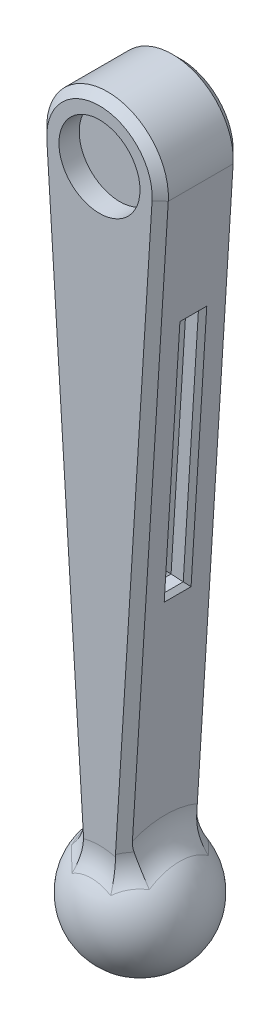
SolidWorks part; units mm, degrees
ref_plane "Front Plane" through (0, 0, 0) normal (0, 0, 1) x (1, 0, 0)
ref_plane "Top Plane" through (0, 0, 0) normal (0, 1, 0) x (1, 0, 0)
ref_plane "Right Plane" through (0, 0, 0) normal (1, 0, 0) x (0, 0, -1)
sketch "Sketch1" plane through (0, 0, 0) normal (0, 0, 1) x (1, 0, 0)
  line L0 (0, 0) -> (0, -160) construction
  line L1 (-14.9707, -0.9375) -> (-4.9902, -160.3125)
  line L2 (14.9707, -0.9375) -> (4.9902, -160.3125)
  arc A0 (14.9707, -0.9375) -> (-14.9707, -0.9375) centre (0, 0) ccw
  arc A1 (-4.9902, -160.3125) -> (4.9902, -160.3125) centre (0, -160) ccw
  dimension "D1" = 30
  dimension "D3" = 10
  dimension "D2" = 160
extrude "Boss-Extrude1" add sketch "Sketch1" along normal mid plane 20
sketch "Sketch2" plane through (0, 0, 10) normal (0, 0, 1) x (1, 0, 0)
  circle A0 centre (0, 0) radius 10
  arc A1 (14.9707, -0.9375) -> (-14.9707, -0.9375) centre (0, 0) ccw construction
  dimension "D1" = 5
extrude "Cut-Extrude1" cut sketch "Sketch2" against normal blind 5
mirror "Mirror1" about plane through (0, 0, 0) normal (0, 0, 1) of "Cut-Extrude1"
sketch "Sketch4" plane through (0, 0, 0) normal (0, 0, 1) x (1, 0, 0)
  line L0 (0, -145) -> (0, -175) construction
  line L1 (0, -145) -> (0, -175)
  arc A0 (0, -145) -> (0, -175) centre (0, -160) ccw
  dimension "D1" = 30
revolve "Revolve1" add sketch "Sketch4" angle 360 about L0
chamfer "Chamfer1" distance 2 angle 45 6 edges at (-10.2929, -75.6348, -10) (0, 15, -10) (10.2929, -75.6348, -10) (-10.2929, -75.6348, 10) (0, 15, 10) (10.2929, -75.6348, 10)
fillet "Fillet1" radius 10 8 edges at (4.679, -148.9659, -9.0198) (0, -148.8197, -10) (-4.679, -148.9659, -9.0198) (-5.8741, -146.198, 0) (-4.679, -148.9659, 9.0198) (0, -148.8197, 10) (4.679, -148.9659, 9.0198) (5.8741, -146.198, 0)
sketch "Sketch5" plane through (14.9707, -0.9375, 0) normal (0.998, -0.0625, 0) x (0, 0, -1)
  line L0 (0, 0) -> (0, -90) construction
  line L1 (-2.3123, -30) -> (2.3123, -30)
  line L2 (-2.3123, -30) -> (-2.3123, -90)
  line L3 (-2.3123, -90) -> (2.3123, -90)
  line L4 (2.3123, -30) -> (2.3123, -90)
  line L5 (-8, 0) -> (8, 0) construction
  dimension "D1" = 60
  dimension "D2" = 30
extrude "Cut-Extrude2" cut sketch "Sketch5" against normal blind 5
chamfer "Chamfer2" distance 1 angle 45 8 edges at (8.1054, -30.5663, 0) (6.2304, -60.5077, -2.3123) (4.3554, -90.449, 0) (6.2304, -60.5077, 2.3123) (11.2207, -60.8202, 2.3123) (9.3457, -90.7615, 0) (11.2207, -60.8202, -2.3123) (13.0957, -30.8788, 0)
mirror "Mirror2" about plane through (0, 0, 0) normal (0, 0, 1) of bodies 105
delete or keep bodies "Body-Delete/Keep 1" type delete bodies bodies 105
sketch "Sketch6" plane through (0, 0, 0) normal (0, 0, 1) x (1, 0, 0)
  line L0 (0, 15) -> (0, -175) construction
  arc A0 (14.9707, -0.9375) -> (-14.9707, -0.9375) centre (0, 0) ccw construction
  arc A1 (-9.7324, -148.586) -> (9.7324, -148.586) centre (0, -160) ccw construction
  point P8 (0, -80)
sketch "Sketch7" plane through (0, 0, 0) normal (0, 0, 1) x (1, 0, 0)
  line L0 (0, 15) -> (0, -175) construction
  arc A0 (-9.7324, -148.586) -> (9.7324, -148.586) centre (0, -160) ccw construction
  point P0 (0, -160)
  point P1 (0, 0)
